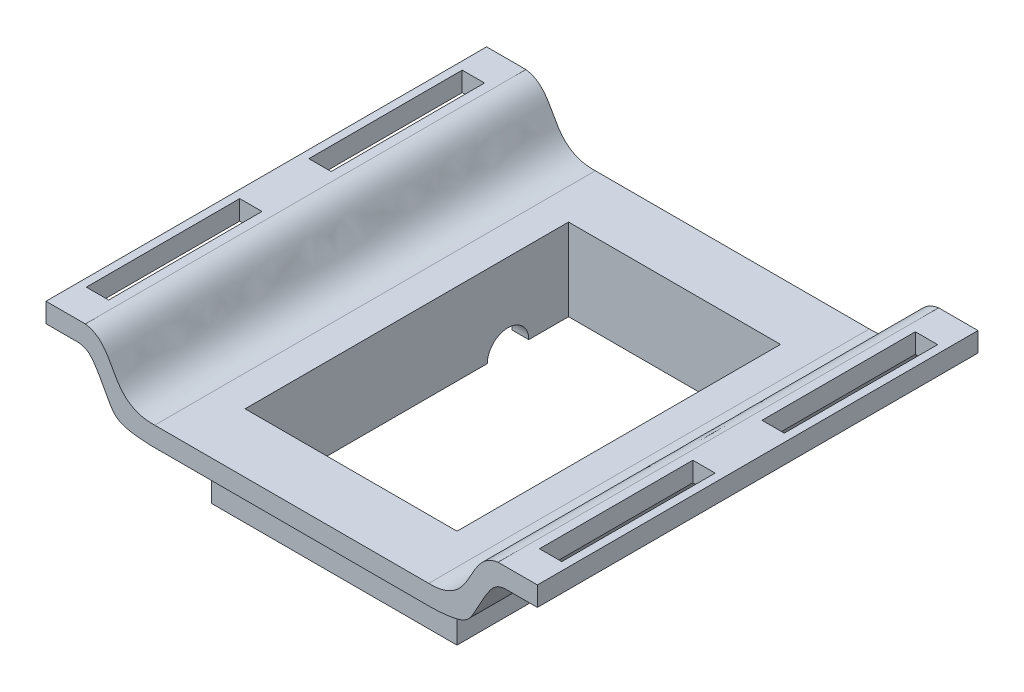
SolidWorks part; units mm, degrees
ref_plane "Front Plane" through (0, 0, 0) normal (0, 0, 1) x (1, 0, 0)
ref_plane "Top Plane" through (0, 0, 0) normal (0, 1, 0) x (1, 0, 0)
ref_plane "Right Plane" through (0, 0, 0) normal (1, 0, 0) x (0, 0, -1)
sketch "Sketch1" plane through (0, 0, 0) normal (0, 0, 1) x (1, 0, 0)
  line L0 (-37, 0) -> (37, 0) construction
  line L3 (-25.1701, -15) -> (25.1701, -15)
  line L4 (-37, -5.5) -> (-44.0504, -5.5)
  line L5 (-44.0504, -5.5) -> (-44.0504, -9)
  line L6 (-44.0504, -9) -> (-38.6222, -9)
  line L7 (-25.1701, -18.5) -> (25.1701, -18.5)
  line L8 (0, 0) -> (0, -48.7682)
  line L12 (-37, 0) -> (-37, -5.5) construction
  line L13 (-37, -15) -> (37, -15) construction
  line L14 (-37, -18.5) -> (37, -18.5) construction
  line L15 (37, 0) -> (37, -5.5) construction
  line L16 (44.0504, -9) -> (38.6222, -9)
  line L17 (44.0504, -5.5) -> (44.0504, -9)
  line L18 (37, -5.5) -> (44.0504, -5.5)
  spline S0 degree 3 poles (-37, -5.5) (-33.4384, -6.048) (-32.1165, -12.1343) (-27.7453, -15.0888) (-24.5568, -15) knots 0 0 0 0 0.567996 1 1 1 1
  spline S1 degree 3 poles (-38.6222, -9) (-37.0136, -8.9402) (-35.0667, -10.7283) (-32.3674, -16.5964) (-30.6986, -18.2872) (-25.1701, -18.5) knots 0 0 0 0 0.269469 0.622038 1 1 1 1
  spline S2 degree 3 poles (38.6222, -9) (37.0136, -8.9402) (35.0667, -10.7283) (32.3674, -16.5964) (30.6986, -18.2872) (25.1701, -18.5) knots 0 0 0 0 0.269469 0.622038 1 1 1 1
  spline S3 degree 3 poles (37, -5.5) (33.4384, -6.048) (32.1165, -12.1343) (27.7453, -15.0888) (24.5568, -15) knots 0 0 0 0 0.567996 1 1 1 1
  point P4 (0, 0)
  point P15 (0, 0)
  point P17 (0, 0)
  point P19 (0, 0)
  point P20 (-35.4447, -10.3504)
  point P21 (0, 0)
  point P24 (0, 0)
  point P26 (-35.7734, -10.3175)
  dimension "D1" = 15
  dimension "D2" = 3.5
extrude "Boss-Extrude1" add sketch "Sketch1" along normal blind 79 contours L6 L8 L4 L5 | L8 region at (-24.8633, -15.4636, 0) region at (12.2784, -15.4593, 0)
sketch "Sketch2" plane through (0, -18.5, 0) normal (0, -1, 0) x (1, 0, 0)
  line L2 (19, 68.3605) -> (-19, 10.3605) construction
  line L3 (-19, 68.3605) -> (19, 10.3605) construction
  line L4 (-19, 68.3605) -> (19, 68.3605)
  line L5 (-19, 68.3605) -> (-19, 10.3605)
  line L6 (-19, 10.3605) -> (19, 10.3605)
  line L7 (19, 68.3605) -> (19, 10.3605)
  line L8 (22, 71.3605) -> (22, 7.3605)
  line L9 (-22, 7.3605) -> (22, 7.3605)
  line L10 (-22, 71.3605) -> (-22, 7.3605)
  line L11 (-22, 71.3605) -> (22, 71.3605)
  point P4 (0, 53.3635)
  dimension "D1" = 58
  dimension "D2" = 38
  dimension "D3" = 3
extrude "Cut-Extrude1" cut sketch "Sketch2" against normal blind 79 contours L5 L6 L7 L4
extrude "Boss-Extrude2" add sketch "Sketch2<4>" along normal blind 11.2
sketch "Sketch2<4>" plane through (0, -18.5, 0) normal (0, -1, 0) x (1, 0, 0) same geometry as "Sketch2"
sketch "Sketch3" plane through (0, -9, 0) normal (0, -1, 0) x (1, 0, 0)
  line L0 (32.5504, 39.5) -> (52.9515, 39.5) construction
  line L1 (32.5504, 79) -> (32.5504, 0) construction
  line L2 (38.6222, 33.3032) -> (42.6222, 5.8032) construction
  line L3 (38.6222, 73.1968) -> (42.6222, 73.1968)
  line L4 (38.6222, 73.1968) -> (38.6222, 45.6968)
  line L5 (38.6222, 45.6968) -> (42.6222, 45.6968)
  line L6 (42.6222, 73.1968) -> (42.6222, 45.6968)
  line L7 (38.6222, 73.1968) -> (42.6222, 45.6968) construction
  line L8 (38.6222, 45.6968) -> (42.6222, 73.1968) construction
  line L9 (38.6222, 5.8032) -> (42.6222, 33.3032) construction
  line L10 (42.6222, 5.8032) -> (42.6222, 33.3032)
  line L11 (38.6222, 33.3032) -> (42.6222, 33.3032)
  line L12 (38.6222, 5.8032) -> (38.6222, 33.3032)
  line L13 (38.6222, 5.8032) -> (42.6222, 5.8032)
  point P4 (40.6222, 59.4468)
  point P13 (40.6222, 19.5532)
  dimension "D1" = 4
  dimension "D2" = 27.5
extrude "Cut-Extrude2" cut sketch "Sketch3" against normal blind 11.2 contours L3 L6 L5 L4 | L11 L10 L13 L12
sketch "Sketch4" plane through (-22, 0, 0) normal (-1, 0, 0) x (0, 0, 1)
  line L0 (71.3605, -29.7) -> (7.3605, -29.7) construction
  circle A0 centre (21.2113, -29.7) radius 3.7197
extrude "Cut-Extrude3" cut sketch "Sketch4" against normal blind 11.2
mirror "Mirror1" about plane through (0, 0, 0) normal (1, 0, 0) of "Cut-Extrude2"
